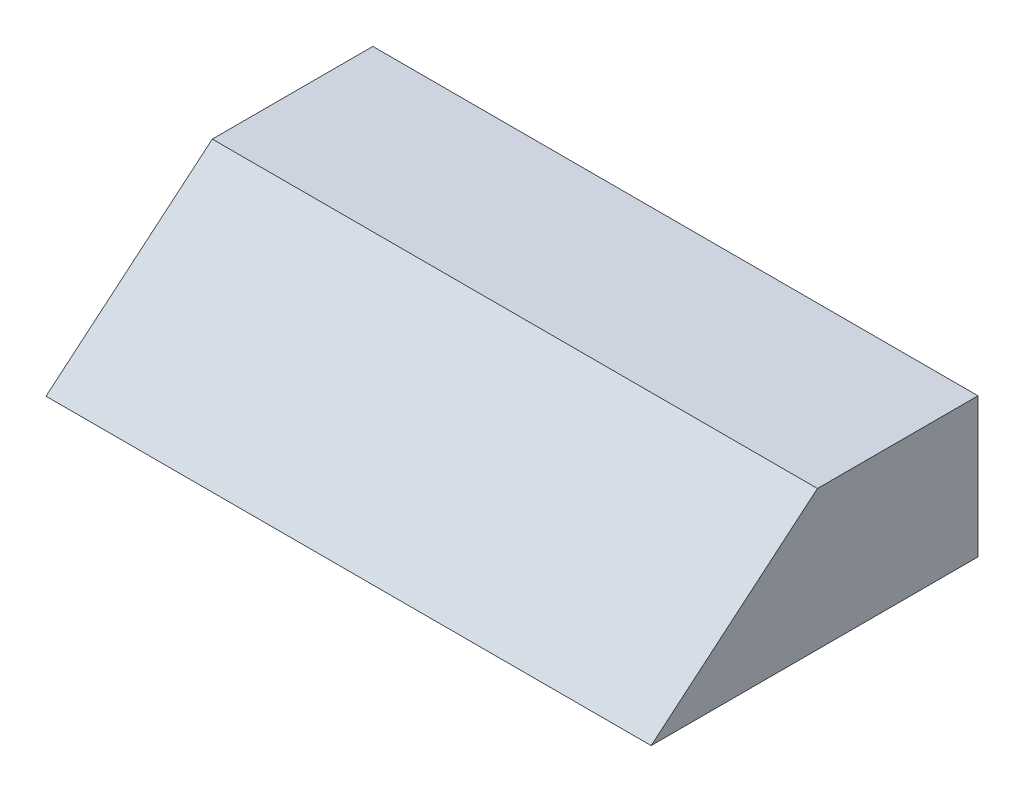
SolidWorks part; units mm, degrees
ref_plane "Alzado" through (0, 0, 0) normal (0, 0, 1) x (1, 0, 0)
ref_plane "Planta" through (0, 0, 0) normal (0, 1, 0) x (1, 0, 0)
ref_plane "Vista lateral" through (0, 0, 0) normal (1, 0, 0) x (0, 0, -1)
sketch "Croquis1" plane through (0, 0, 0) normal (1, 0, 0) x (0, 0, -1)
  line L0 (0, 0) -> (105.85, 0)
  line L1 (105.85, 0) -> (105.85, 45.19)
  line L2 (105.85, 45.19) -> (53.8553, 45.19)
  line L3 (0, 0) -> (53.8553, 45.19)
  line L4 (105.8531, 0) -> (105.8531, 45.19) construction
  line L5 (105.85, 0) -> (0, 0) construction
  line L6 (53.8553, 45.19) -> (105.85, 45.19) construction
  dimension "D1" = 105.85
  dimension "D2" = 45.19
  dimension "D3" = 140
extrude "Saliente-Extruir1" add sketch "Croquis1" along normal blind 196
shell "Vaciado1" thickness 4 removed face at (98, 0, -52.925)
